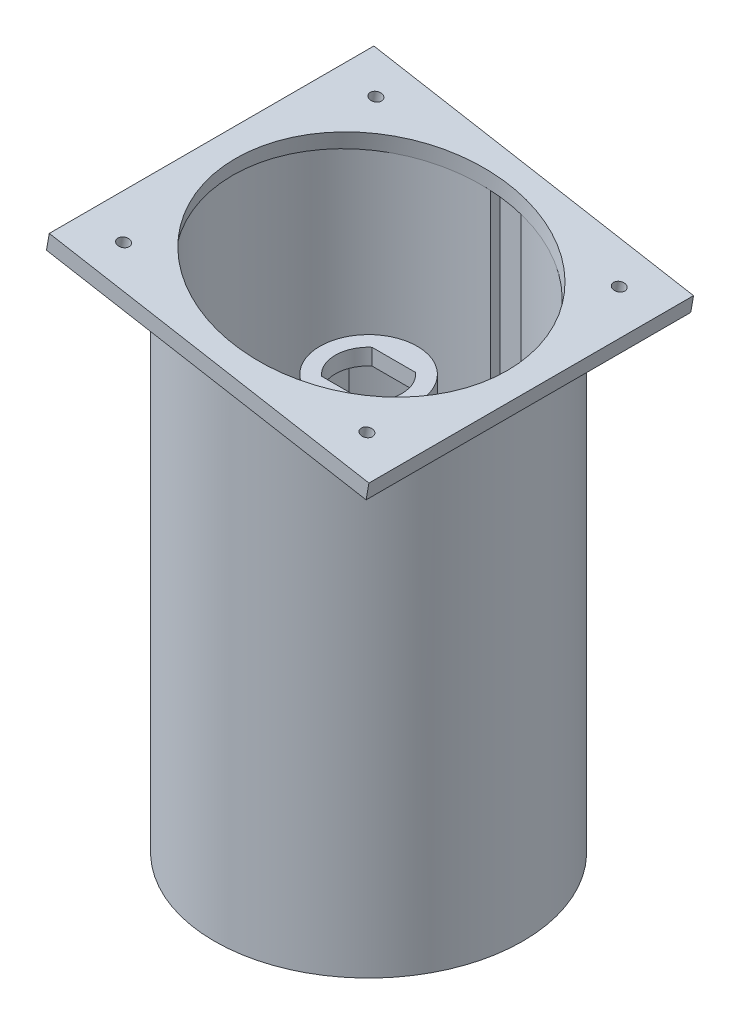
SolidWorks part; units mm, degrees
ref_plane "Front Plane" through (0, 0, 0) normal (0, 0, 1) x (1, 0, 0)
ref_plane "Top Plane" through (0, 0, 0) normal (0, 1, 0) x (1, 0, 0)
ref_plane "Right Plane" through (0, 0, 0) normal (1, 0, 0) x (0, 0, -1)
ref_axis "Axis2" through (0, 0, 52.25) along (0, 0, -1)
ref_plane "Plane8" through (0, 0, 0) normal (0.1736, 0.9848, 0) x (0, 0, -1)
ref_plane "Plane9" through (26.0472, 147.7212, 0) normal (0.1736, 0.9848, 0) x (0, 0, -1)
sketch "Sketch1" plane through (0, 0, 0) normal (0, 1, 0) x (1, 0, 0)
  line L0 (0, 42.5) -> (0, -42.5) construction
  line L1 (-4.75, -42.2337) -> (-4.75, -45.2337)
  line L2 (-4.75, -45.2337) -> (4.75, -45.2337)
  line L3 (4.75, -42.2337) -> (4.75, -45.2337)
  line L4 (-42.5, 0) -> (42.5, 0) construction
  line L5 (4.75, 42.2337) -> (4.75, 45.2337)
  line L6 (-4.75, 45.2337) -> (4.75, 45.2337)
  line L7 (-4.75, 42.2337) -> (-4.75, 45.2337)
  circle A0 centre (0, 0) radius 47.5
  arc A1 (-4.75, 42.2337) -> (-4.75, -42.2337) centre (0, 0) ccw
  arc A2 (4.75, -42.2337) -> (4.75, 42.2337) centre (0, 0) ccw
  dimension "D2" = 95
  dimension "D1" = 85
  dimension "D3" = 9.5
  dimension "D4" = 3
  dimension "D5" = 4.75
sketch "Sketch2" plane through (0, 0, 0) normal (0, 1, 0) x (1, 0, 0)
  line L0 (0, 0) -> (0, -37.5) construction
  circle A0 centre (0, 0) radius 47.5
  circle A1 centre (0, 0) radius 37.5
  dimension "D2" = 95
  dimension "D1" = 75
extrude "Boss-Extrude2" add sketch "Sketch2" along normal blind 5
extrude "Boss-Extrude4" add sketch "Sketch1" along normal up to surface (152.314 mm away) up to plane "Plane9"
sketch "Sketch9" plane through (26.0472, 147.7212, 0) normal (0.1736, 0.9848, 0) x (0, 0, -1)
  line L1 (50, 76.449) -> (-50, 76.449)
  line L2 (50, 76.449) -> (50, -23.551)
  line L3 (50, -23.551) -> (-50, -23.551)
  line L4 (-50, 76.449) -> (-50, -23.551)
  line L5 (50, 76.449) -> (-50, -23.551) construction
  line L6 (50, -23.551) -> (-50, 76.449) construction
  circle A0 centre (0, 26.449) radius 42.5
  point P6 (0, 0)
  dimension "D1" = 100
  dimension "D2" = 100
extrude "Boss-Extrude7" add sketch "Sketch9" along normal blind 5
sketch "Sketch10" plane through (26.0472, 147.7212, 0) normal (0.1736, 0.9848, 0) x (0, 0, -1)
  line L0 (0, 76.449) -> (0, -23.551) construction
  line L1 (50, 76.449) -> (-50, 76.449) construction
  line L2 (-50, -23.551) -> (50, -23.551) construction
  line L3 (-50, 26.449) -> (50, 26.449) construction
  line L4 (-50, 76.449) -> (-50, -23.551) construction
  line L5 (50, -23.551) -> (50, 76.449) construction
  circle A0 centre (-38.869, 64.503) radius 1.75
  circle A1 centre (38.869, 64.503) radius 1.75
  circle A2 centre (38.869, -11.6049) radius 1.75
  circle A3 centre (-38.869, -11.6049) radius 1.75
  dimension "D1" = 3.5
extrude "Cut-Extrude2" cut sketch "Sketch10" along normal blind 5
ref_plane "Plane10" through (0, 100, 0) normal (0, 1, 0) x (1, 0, 0)
sketch "Sketch11" plane through (0, 100, 0) normal (0, 1, 0) x (1, 0, 0)
  line L0 (-44.8723, 4.7251) -> (-8.8133, 4.7251)
  line L1 (-43.7925, -4.6681) -> (-8.8436, -4.6681)
  line L2 (0, 10) -> (0, -10) construction
  line L3 (43.7925, -4.6681) -> (8.8436, -4.6681)
  line L4 (44.8723, 4.7251) -> (8.8133, 4.7251)
  line L5 (-44.8723, 4.7251) -> (-43.7925, -4.6681)
  line L6 (44.8723, 4.7251) -> (43.7925, -4.6681)
  circle A0 centre (0, 0) radius 3.75
  arc A1 (-8.8436, -4.6681) -> (8.8436, -4.6681) centre (0, 0) ccw
  arc A3 (8.8133, 4.7251) -> (-8.8133, 4.7251) centre (0, 0) ccw
  dimension "D1" = 7.5
  dimension "D2" = 20
extrude "Boss-Extrude9" add sketch "Sketch11" along normal blind 5
ref_plane "Plane11" through (0, 122.5, 0) normal (0, 1, 0) x (1, 0, 0)
sketch "Sketch12" plane through (0, 122.5, 0) normal (0, 1, 0) x (1, 0, 0)
  line L0 (-6.7082, -7.75) -> (6.7082, -7.75)
  line L2 (6.7082, 7.75) -> (-6.7082, 7.75)
  arc A0 (-6.7082, 7.75) -> (-6.7082, -7.75) centre (0, 0) ccw
  arc A1 (6.7082, -7.75) -> (6.7082, 7.75) centre (0, 0) ccw
  circle A2 centre (0, 0) radius 15
  dimension "D2" = 30
  dimension "D3" = 15.5
  dimension "D1" = 10.25
extrude "Boss-Extrude10" add sketch "Sketch12" along normal blind 5 separate body
sketch "Sketch13" plane through (0, 122.5, 0) normal (0, 1, 0) x (1, 0, 0)
  line L0 (-8.8133, 4.7251) -> (-42.2365, 4.7251) construction
  line L1 (-14.2363, 4.7251) -> (-10.7382, 4.7251)
  line L2 (-14.2363, 4.7251) -> (-14.2363, -4.6368)
  line L3 (-14.2363, -4.6368) -> (-10.7382, -4.6368)
  line L4 (-10.7382, 4.7251) -> (-10.7382, -4.6368)
  line L5 (0, 7.75) -> (0, -6.7661) construction
  line L6 (6.7082, 7.75) -> (-6.7082, 7.75) construction
  line L7 (0, -52.25) -> (0, 52.25) construction
  line L8 (14.2363, -4.6368) -> (10.7382, -4.6368)
  line L9 (14.2363, 4.7251) -> (14.2363, -4.6368)
  line L10 (14.2363, 4.7251) -> (10.7382, 4.7251)
  line L11 (10.7382, 4.7251) -> (10.7382, -4.6368)
  circle A0 centre (0, 0) radius 15 construction
extrude "Boss-Extrude11" add sketch "Sketch13" against normal up to surface (17.5 mm away) up to face at (0, 105, 3.75)
equation "\"BallBearingDiameter\" = 22mm"
equation "\"SmallTubeOD\" = 75mm"
equation "\"SmallTubeID\"= \"SmallTubeOD\" - \"WallThickness\" * 2"
equation "\"ZTravel\"= 20mm"
equation "\"WallThickness\"= 5mm"
equation "\"D1@Boss-Extrude1\"= \"ZTravel\""
equation "\"D1@Sketch4\"=\"SmallTubeID\""
equation "\"RestrictingFlangeOD\"= \"SmallTubeOD\" + 10mm"
equation "\"D2@Sketch4\"=\"RestrictingFlangeOD\""
equation "\"D1@Boss-Extrude3\"=\"WallThickness\""
equation "\"HexNutDiameter\" = 13mm"
equation "\"D1@Sketch7\"=\"HexNutDiameter\""
equation "\"D3@Sketch4\"=\"HexNutDiameter\"+5"
equation "\"D2@Sketch1\"=\"SmallTubeOD\"+20"
equation "\"D2@Sketch2\"=\"SmallTubeOD\"+20"
equation "\"D1@Sketch2\"=\"SmallTubeOD\""
equation "\"D1@Sketch1\"=\"SmallTubeOD\"+10"
